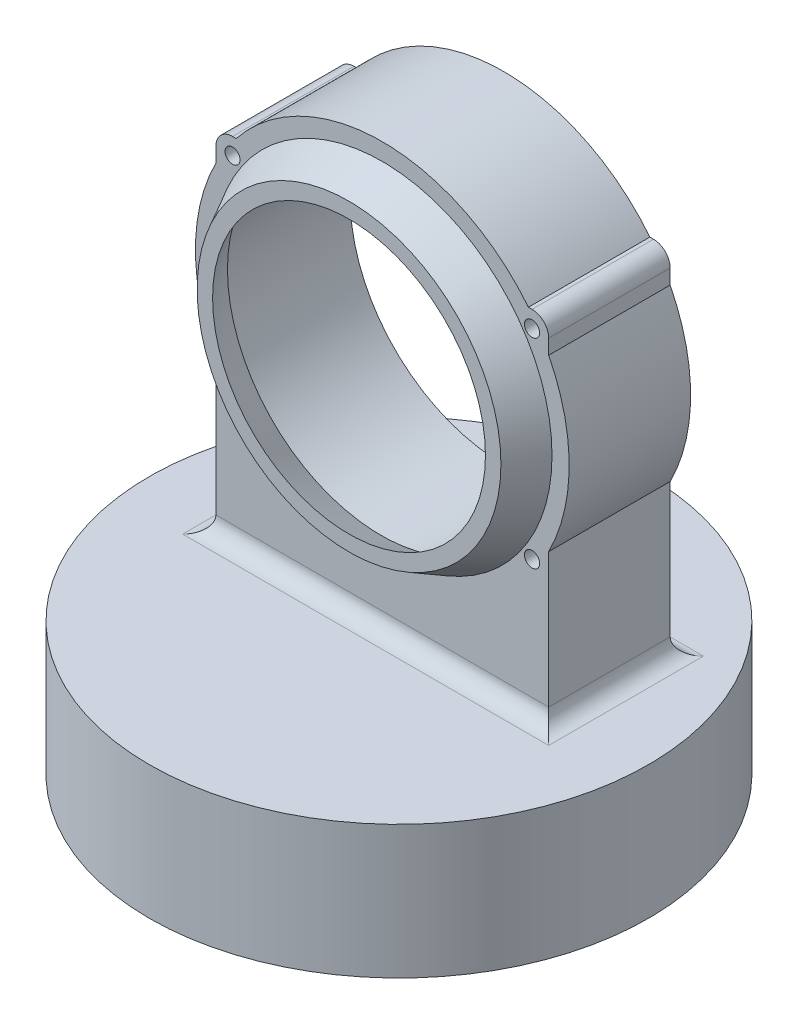
SolidWorks part; units mm, degrees
ref_plane "Alzado" through (0, 0, 0) normal (0, 0, 1) x (1, 0, 0)
ref_plane "Planta" through (0, 0, 0) normal (0, 1, 0) x (1, 0, 0)
ref_plane "Vista lateral" through (0, 0, 0) normal (1, 0, 0) x (0, 0, -1)
sketch "Croquis1" plane through (0, 0, 0) normal (0, 1, 0) x (1, 0, 0)
  circle A0 centre (0, 0) radius 75
  dimension "D1" = 150
extrude "Saliente-Extruir1" add sketch "Croquis1" along normal blind 40
sketch "Croquis3" plane through (0, 0, 0) normal (0, 0, 1) x (1, 0, 0)
  line L0 (43.907, 146.0004) -> (45, 146.0004)
  line L1 (50, 85.45) -> (50, 40)
  line L2 (0, 0) -> (0, 85.4991) construction
  line L10 (-45, 146.0004) -> (-43.907, 146.0004)
  line L11 (-50, 141.0004) -> (-50, 136.5508)
  line L12 (-50, 40) -> (50, 40)
  line L13 (50, 141.0004) -> (50, 136.5508)
  line L14 (75, 40) -> (-75, 40) construction
  line L15 (-50, 85.45) -> (-50, 40)
  circle A0 centre (0, 111.0004) radius 46.15
  circle A1 centre (0, 111.0004) radius 56.15
  arc A2 (45, 146.0004) -> (50, 141.0004) centre (45, 141.0004) cw
  arc A3 (-45, 146.0004) -> (-50, 141.0004) centre (-45, 141.0004) ccw
  point P5 (-0.8152, 30)
  point P17 (50, 146.0004)
  point P20 (-50, 146.0004)
  dimension "D4" = 92.3
  dimension "D6" = 5
  dimension "D8" = 71.0004
  dimension "D1" = 100
  dimension "D2" = 10
  dimension "D3" = 35
  dimension "D5" = 50
  dimension "D7" = 45.45
extrude "Saliente-Extruir2" add sketch "Croquis3" against normal blind 36.5 from offset 5 contours A1 L15 L12 | A1 L12 L1 | L10 A3 L11 A1 | A2 L0 A1 L13 | A1 | A0 region at (47.8302, 142.4889, 0) region at (-47.8302, 142.4889, 0) region at (0, 53.3283, 0)
sketch "Croquis5" plane through (0, 0, 5) normal (0, 0, 1) x (1, 0, 0)
  circle A0 centre (0, 111.0004) radius 41
  circle A1 centre (0, 111.0004) radius 51
  circle A2 centre (0, 111.0004) radius 46.15 construction
  circle A3 centre (0, 111.0004) radius 46.15 construction
  dimension "D1" = 82
  dimension "D2" = 10
extrude "Saliente-Extruir3" add sketch "Croquis5" along normal blind 10
chamfer "Chaflán1" distance 10 angle 28.15 1 edges at (41, 111.0004, 5) first distance on face at (41, 111.0004, 15)
chamfer "Chaflán2" distance 10 angle 28.15 1 edges at (51, 111.0004, 15) first distance on face at (51, 111.0004, 15)
fillet "Redondeo1" radius 5 4 edges at (0, 40, -31.5) (-50, 40, -13.25) (0, 40, 5) (50, 40, -13.25)
sketch "Croquis7" plane through (0, 0, -31.5) normal (0, 0, -1) x (-1, 0, 0)
  line L0 (0.0118, 110.9868) -> (71.2114, 110.9868) construction
  circle A0 centre (45, 141.0004) radius 2.2483
  circle A1 centre (-45, 141.0004) radius 2.2831
  circle A2 centre (-45, 80.9733) radius 2.2831
  circle A3 centre (45, 80.9733) radius 2.2483
  dimension "D3" = 4.4965
  dimension "D1" = 30.0136
  dimension "D2" = 44.9882
extrude "Cortar-Extruir2" cut sketch "Croquis7" against normal through all
sketch "Croquis8" plane through (0, 0, 0) normal (0, -1, 0) x (1, 0, 0)
  circle A0 centre (0, 0) radius 61.2271
  circle A1 centre (-2.6474, 28.2744) radius 2.5
  circle A2 centre (24.208, -14.8467) radius 2.5
  circle A3 centre (2.6474, -28.2744) radius 2.5
  circle A4 centre (-24.208, 14.8467) radius 2.5
  dimension "D1" = 122.4541
  dimension "D2" = 5
extrude "Cortar-Extruir3" cut sketch "Croquis8" against normal blind 1.5 contours A0
extrude "Cortar-Extruir4" cut sketch "Croquis8<3>" against normal blind 10 contours A1 | A2 | A3 | A4
sketch "Croquis8<3>" plane through (0, 0, 0) normal (0, -1, 0) x (1, 0, 0) same geometry as "Croquis8"
